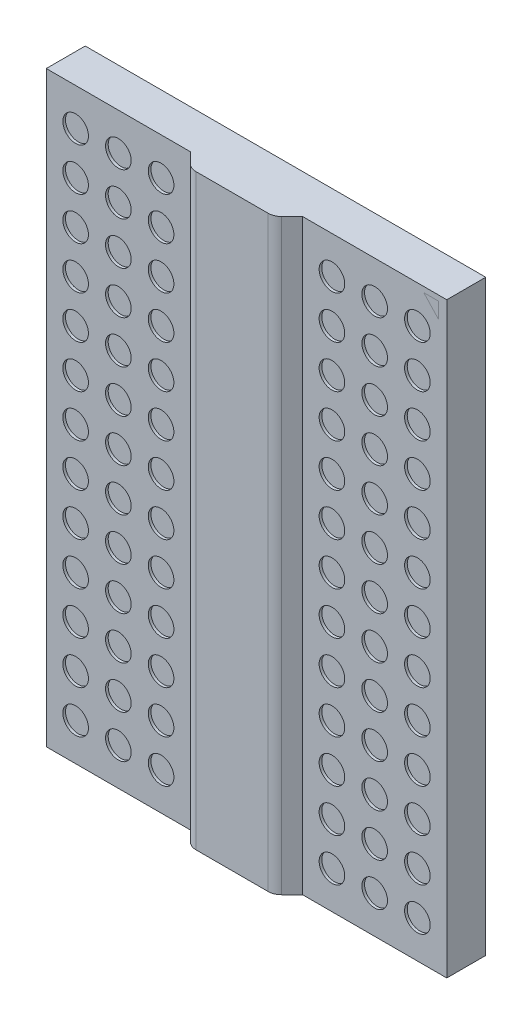
SolidWorks part; units mm, degrees
ref_plane "Front Plane" through (0, 0, 0) normal (0, 0, 1) x (1, 0, 0)
ref_plane "Top Plane" through (0, 0, 0) normal (0, 1, 0) x (1, 0, 0)
ref_plane "Right Plane" through (0, 0, 0) normal (1, 0, 0) x (0, 0, -1)
sketch "Sketch1" plane through (0, 0, 0) normal (0, 0, 1) x (1, 0, 0)
  line L1 (-3.75, 5.5) -> (3.75, 5.5)
  line L2 (-3.75, 5.5) -> (-3.75, -5.5)
  line L3 (-3.75, -5.5) -> (3.75, -5.5)
  line L4 (3.75, 5.5) -> (3.75, -5.5)
  line L5 (0, -5.5) -> (0, 5.5) construction
  line L6 (-3.75, 0) -> (3.75, 0) construction
  point P0 (0, 0)
  dimension "D1" = 11
  dimension "D2" = 7.5
extrude "Boss-Extrude1" add sketch "Sketch1" along normal blind 1.1
sketch "Sketch2" plane through (0, 0, 1.1) normal (0, 0, 1) x (1, 0, 0)
  line L0 (0, 5.5) -> (0, -5.5) construction
  line L1 (-3.75, -5.5) -> (3.75, -5.5) construction
  line L2 (0, 0) -> (3.75, 0) construction
  line L3 (3.75, -5.5) -> (3.75, 5.5) construction
  line L4 (-3.75, -5.5) -> (-1.05, -5.5)
  line L5 (3.75, 5.5) -> (1.05, 5.5)
  line L6 (3.75, 5.5) -> (3.75, -5.5)
  line L7 (3.75, -5.5) -> (1.05, -5.5)
  line L8 (1.05, 5.5) -> (1.05, -5.5)
  line L9 (-1.05, 5.5) -> (-1.05, -5.5)
  line L10 (-3.75, 5.5) -> (-1.05, 5.5)
  line L11 (-3.75, 5.5) -> (-3.75, -5.5)
  point P6 (0, 0)
  dimension "D1" = 1.05
extrude "Cut-Extrude1" cut sketch "Sketch2" against normal blind 0.37
sketch "Sketch3" plane through (0, 0, 1.1) normal (0, 0, 1) x (1, 0, 0)
  line L1 (-1.05, 5.5) -> (1.05, 5.5)
  line L2 (-1.05, 5.5) -> (-1.05, -5.5)
  line L3 (-1.05, -5.5) -> (1.05, -5.5)
  line L4 (1.05, 5.5) -> (1.05, -5.5)
extrude "Cut-Extrude2" cut sketch "Sketch3" against normal blind 0.1
chamfer "Chamfer1" distance 0.27 angle 45 2 edges at (1.05, 0, 1) (-1.05, 0, 1)
fillet "Fillet1" radius 0.25 2 edges at (0.78, 0, 1) (-0.78, 0, 1)
sketch "Sketch4" plane through (0, 0, 0.73) normal (0, 0, 1) x (1, 0, 0)
  line L0 (0, 0) -> (-3.75, 0) construction
  line L1 (-3.75, 5.5) -> (-3.75, -5.5) construction
  circle A0 centre (-1.6, 0) radius 0.24
  dimension "D1" = 0.48
  dimension "D2" = 1.6
extrude "Cut-Extrude3" cut sketch "Sketch4" against normal blind 0.05
pattern_linear "LPattern1" count 3 spacing 0.8 along (-1, 0, 0) count 7 spacing 0.8 along (0, -1, 0) of "Cut-Extrude3"
mirror "Mirror1" about plane through (0, 0, 0) normal (0, 1, 0) of "LPattern1"
mirror "Mirror2" about plane through (0, 0, 0) normal (1, 0, 0) of "Mirror1", "LPattern1"
sketch "Sketch6" plane through (0, 0, 0.73) normal (0, 0, 1) x (1, 0, 0)
  line L0 (73.4053, 304.3994) -> (382.7386, 304.3994) construction
  line L2 (3.32, 5.4) -> (3.6, 5.4)
  line L3 (3.6, 5.4) -> (3.6, 5.1)
  line L5 (3.6, 5.1) -> (3.32, 5.4)
  line L6 (3.75, 5.5) -> (1.05, 5.5) construction
  line L7 (3.75, -5.5) -> (3.75, 5.5) construction
  dimension "D1" = 0.28
  dimension "D2" = 0.3
  dimension "D3" = 0.1
  dimension "D4" = 0.15
split line "Split Line1"
sketch "Sketch8" plane through (0, 0, 0) normal (0, 0, -1) x (-1, 0, 0)
  line L0 (172.3048, -34.1469) -> (172.3048, -192.8136) construction
  line L3 (-3.75, -5.5) -> (-3.75, 5.5) construction
  line L5 (-3.75, 5.5) -> (3.75, 5.5) construction
  circle A0 centre (-2.35, 4.2) radius 0.3
  dimension "D1" = 0.6
  dimension "D2" = 1.4
  dimension "D3" = 1.3
split line "Split Line2"
sketch "Sketch9" plane through (0, 0, 0) normal (0, 0, -1) x (-1, 0, 0)
  line L0 (1.6902, -0.8719) -> (1.6902, -2.6033) construction
  line L1 (0.4002, -0.3771) -> (0.4002, -4.6525) construction
  line L2 (-0.9121, -0.2095) -> (-0.9121, -1.9121) construction
  line L3 (-2.7668, 2.4138) -> (-2.7668, -3.0393) construction
  line L4 (1.6902, -3.0001) -> (1.6902, -4.681) construction
  line L5 (-0.9121, -2.3445) -> (-0.9121, -4.6525) construction
  text T0 "SEC" font "Arial Unicode MS" height 1
  text T1 "649" font "Arial Unicode MS" height 1
  text T2 "K4A8G08" font "Arial Unicode MS" height 1
  text T3 "5WB " font "Arial Unicode MS" height 1
  text T4 "BCPB" font "Arial Unicode MS" height 1
  text T5 "GEJ55511C" font "Arial Unicode MS" height 1
split line "Split Line3"
